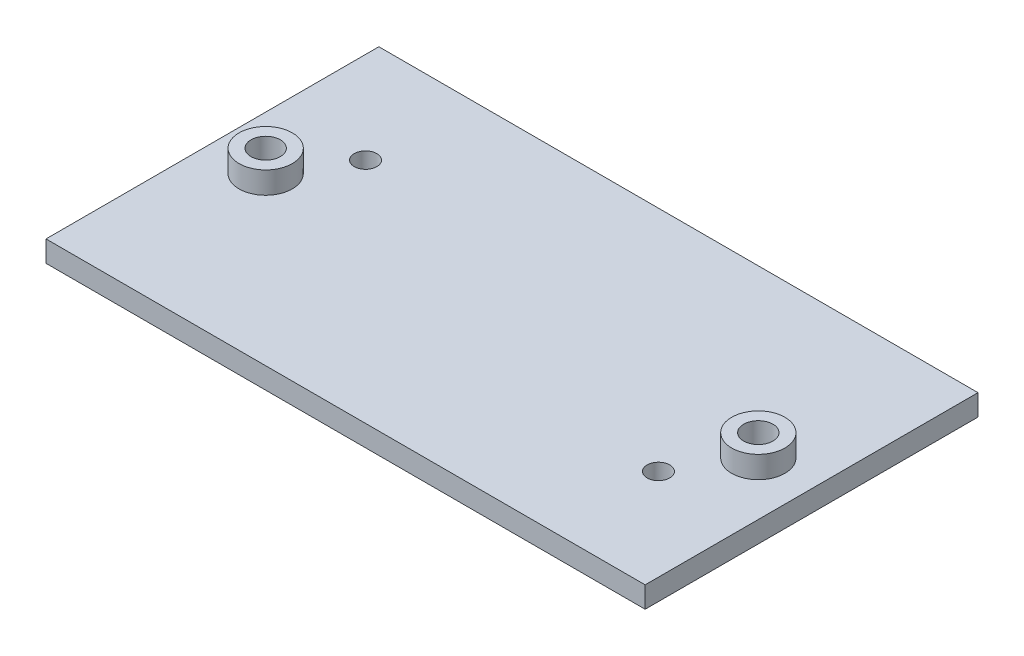
SolidWorks part; units mm, degrees
ref_plane "Front Plane" through (0, 0, 0) normal (0, 0, 1) x (1, 0, 0)
ref_plane "Top Plane" through (0, 0, 0) normal (0, 1, 0) x (1, 0, 0)
ref_plane "Right Plane" through (0, 0, 0) normal (1, 0, 0) x (0, 0, -1)
sketch "Plate Sketch" plane through (0, 0, 0) normal (0, 1, 0) x (1, 0, 0)
  line L0 (-45, 25) -> (45, 25)
  line L1 (45, 25) -> (45, -25)
  line L2 (45, -25) -> (-45, -25)
  line L3 (-45, -25) -> (-45, 25)
  circle A0 centre (-37, 0) radius 2.2
  circle A1 centre (37, 0) radius 2.2
  circle A2 centre (-31.25, 9.25) radius 1.7
  circle A3 centre (31.25, -9.25) radius 1.7
extrude "Plate" add sketch "Plate Sketch" along normal blind 3.18 from offset 92.57
ref_axis "Engine Axis" through (49.5, 0, 0) along (-1, 0, 0)
sketch "Pads Sketch" plane through (0, 0, 0) normal (0, 1, 0) x (1, 0, 0)
  circle A0 centre (-37, 0) radius 4
  circle A1 centre (37, 0) radius 4
  circle A2 centre (-37, 0) radius 2.2
  circle A3 centre (37, 0) radius 2.2
extrude "Pads" add sketch "Pads Sketch" along normal blind 3.3 from offset 95.75
